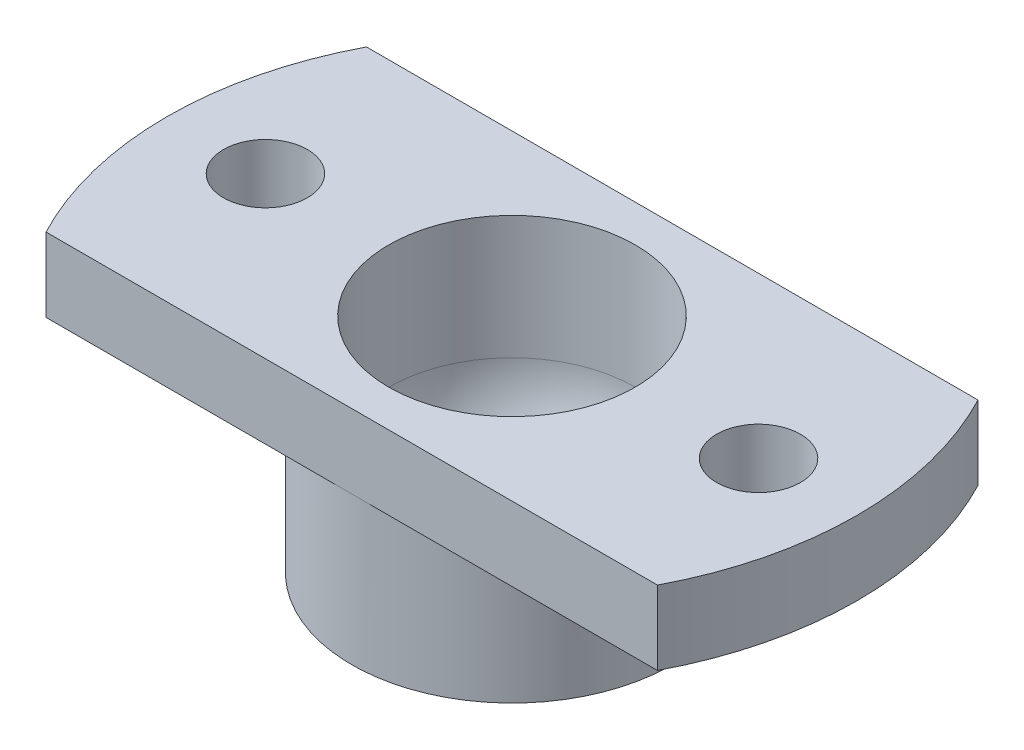
SolidWorks part; units mm, degrees
material "ABS"
ref_plane "Front Plane" through (0, 0, 0) normal (0, 0, 1) x (1, 0, 0)
ref_plane "Top Plane" through (0, 0, 0) normal (0, 1, 0) x (1, 0, 0)
ref_plane "Right Plane" through (0, 0, 0) normal (1, 0, 0) x (0, 0, -1)
sketch "Sketch1" plane through (0, 0, 0) normal (1, 0, 0) x (0, 0, -1)
  line L0 (-14, 5) -> (-5, 5)
  line L1 (-14, 5) -> (-14, 2)
  line L2 (0, 0) -> (0, 10.3505) construction
  line L3 (-14, 2) -> (-6.5, 2)
  line L4 (-5, 0) -> (-5, 5)
  line L6 (-6.5, -4) -> (-3, -4)
  line L7 (-6.5, -4) -> (-6.5, 2)
  arc A0 (-5, 0) -> (-3, -4) centre (0, 0) ccw
  dimension "D1" = 14
  dimension "D2" = 5
  dimension "D4" = 3
  dimension "D5" = 7.5
  dimension "D6" = 4
revolve "Revolve1" add sketch "Sketch1" angle 360 about L2
hole_wizard "M3 Clearance Hole1" positions "Sketch4" profile "Sketch3" hole size "M3" standard "ISO"
sketch "Sketch4" plane through (0, 2, 0) normal (0, -1, 0) x (-1, 0, 0)
  point P0 (10, 0)
  dimension "D1" = 10
sketch "Sketch3" plane through (-10, 2, 0) normal (1, 0, 0) x (0, 0, -1)
  line L0 (0, 0) -> (0, 11.0215)
  line L1 (0, 11.0215) -> (1.7, 10)
  line L2 (1.7, 10) -> (1.7, 0)
  line L5 (1.7, 0) -> (0, 0)
  line L10 (0, 11.0215) -> (-1.7, 10) construction
  line L11 (0, -6.35) -> (0, 107.95) construction
  dimension "Hole Dia." = 3.4
  dimension "Hole Depth" = 10
  dimension "Drill Angle" = 118
pattern_circular "CirPattern2" count 2 over 360 of "M3 Clearance Hole1"
sketch "Sketch5" plane through (0, 2, 0) normal (0, -1, 0) x (1, 0, 0)
  line L1 (-17.0763, 6.5) -> (20.9148, 6.5)
  line L2 (-17.0763, 6.5) -> (-17.0763, -6.5)
  line L3 (-17.0763, -6.5) -> (20.9148, -6.5)
  line L4 (20.9148, 6.5) -> (20.9148, -6.5)
  line L5 (-23.7253, 17.7727) -> (26.7016, 17.7727)
  line L6 (-23.7253, 17.7727) -> (-23.7253, -15.7319)
  line L7 (-23.7253, -15.7319) -> (26.7016, -15.7319)
  line L8 (26.7016, 17.7727) -> (26.7016, -15.7319)
  circle A0 centre (0, 0) radius 6.5 construction
  circle A1 centre (0, 0) radius 6.5 construction
extrude "Cut-Extrude1" cut sketch "Sketch5" against normal through all
